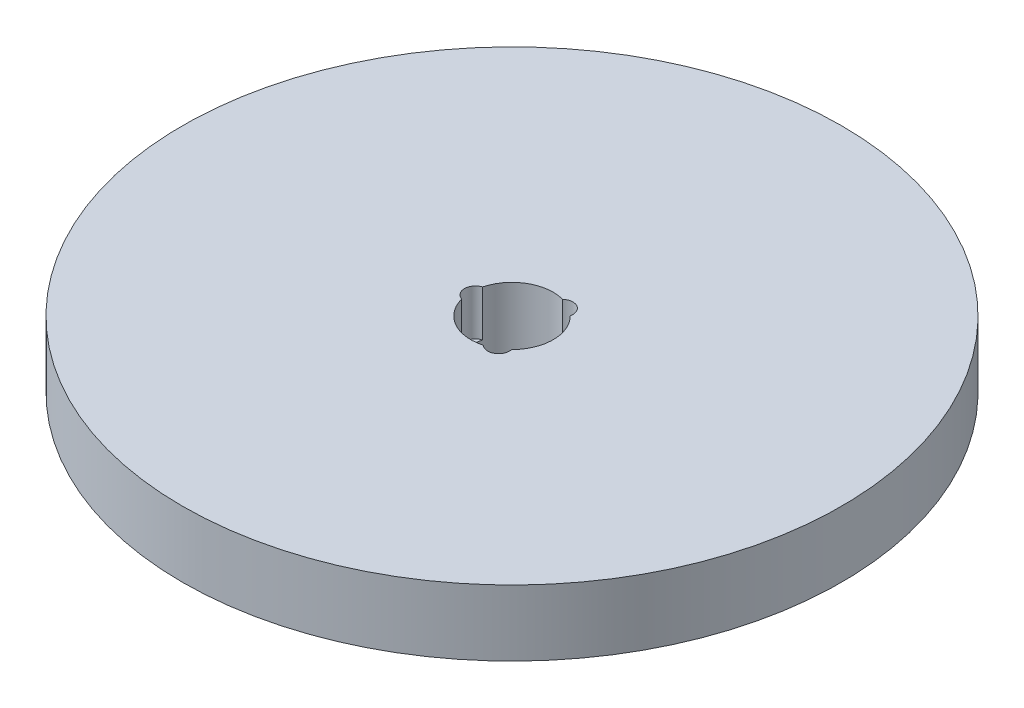
SolidWorks part; units mm, degrees
ref_plane "Front Plane" through (0, 0, 0) normal (0, 0, 1) x (1, 0, 0)
ref_plane "Top Plane" through (0, 0, 0) normal (0, 1, 0) x (1, 0, 0)
ref_plane "Right Plane" through (0, 0, 0) normal (1, 0, 0) x (0, 0, -1)
sketch "Sketch1" plane through (0, 0, 0) normal (0, 1, 0) x (1, 0, 0)
  circle A0 centre (0, 0) radius 60
  dimension "FLANGE_OD" = 120
extrude "Boss-Extrude1" add sketch "Sketch1" along normal blind 12
sketch "Sketch2" plane through (0, 0, 0) normal (0, 1, 0) x (1, 0, 0)
  circle A0 centre (0, 0) radius 7.5
  dimension "BORE_D" = 15
extrude "Cut-Extrude1" cut sketch "Sketch2" along normal through all
sketch "Sketch3" plane through (0, 12, 0) normal (0, 1, 0) x (1, 0, 0)
  circle A0 centre (0, 0) radius 6.6573 construction
  circle A1 centre (-6.6573, 0) radius 1.9869
  dimension "BOLT_D" = 3.9739
  dimension "BOLT_PCD" = 13.3146
extrude "Cut-Extrude2" cut sketch "Sketch3" against normal blind 8.3616
pattern_circular "CirPattern1" count 3 over 360 about axis through (0, 0, 0) along (0, 1, 0) of "Cut-Extrude2"
